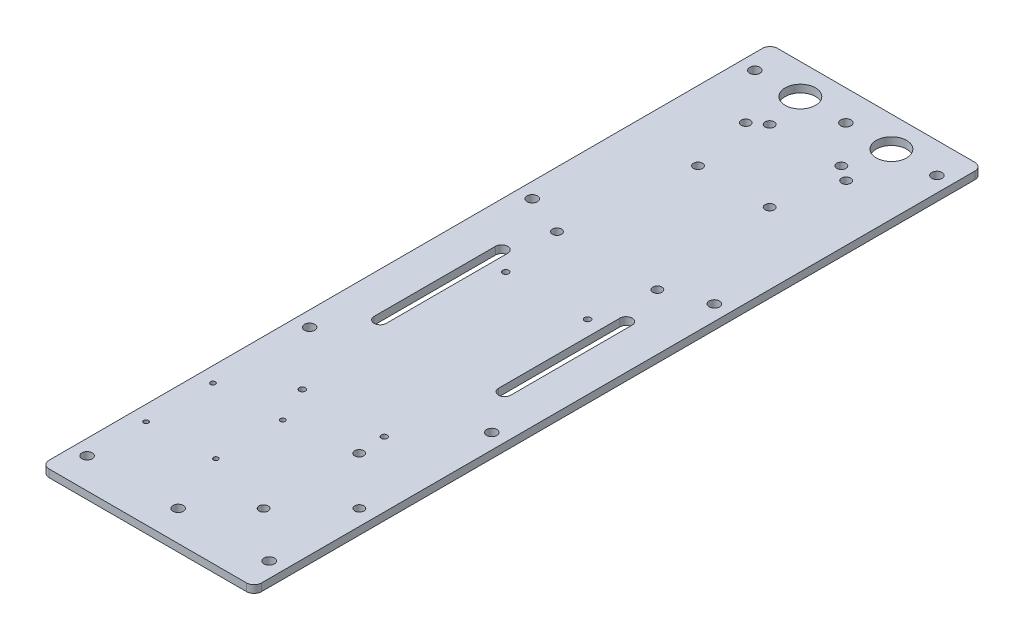
SolidWorks part; units mm, degrees
ref_plane "Front Plane" through (0, 0, 0) normal (0, 0, 1) x (1, 0, 0)
ref_plane "Top Plane" through (0, 0, 0) normal (0, 1, 0) x (1, 0, 0)
ref_plane "Right Plane" through (0, 0, 0) normal (1, 0, 0) x (0, 0, -1)
sketch "Sketch2" plane through (0, 0, 0) normal (0, 1, 0) x (1, 0, 0)
  line L0 (-44.45, 0) -> (44.45, 0) construction
  line L1 (-41.275, 152.4) -> (41.275, 152.4)
  line L2 (-44.45, 149.225) -> (-44.45, -149.225)
  line L3 (-41.275, -152.4) -> (41.275, -152.4)
  line L4 (44.45, 149.225) -> (44.45, -149.225)
  line L5 (0, 152.4) -> (0, -152.4) construction
  arc A0 (-44.45, -149.225) -> (-41.275, -152.4) centre (-41.275, -149.225) ccw
  arc A1 (41.275, -152.4) -> (44.45, -149.225) centre (41.275, -149.225) ccw
  arc A2 (41.275, 152.4) -> (44.45, 149.225) centre (41.275, 149.225) cw
  arc A3 (-41.275, 152.4) -> (-44.45, 149.225) centre (-41.275, 149.225) ccw
  point P8 (0, 0)
  point P13 (-44.45, -152.4)
  point P16 (44.45, -152.4)
  point P21 (-44.45, 152.4)
  dimension "D3" = 3.175
  dimension "D1" = 304.8
  dimension "D2" = 88.9
extrude "Plate Thickness" add sketch "Sketch2" along normal blind 3.175 contours L2 A0 L3 A1 L4 A2 L1 A3
sketch "Sketch3" plane through (0, 3.175, 0) normal (0, 1, 0) x (1, 0, 0)
  line L0 (-44.45, 149.225) -> (-44.45, -149.225) construction
  line L1 (-41.275, 152.4) -> (41.275, 152.4) construction
  line L4 (0, 152.4) -> (0, -152.4) construction
  line L5 (-41.275, -152.4) -> (41.275, -152.4) construction
  line L6 (-41.275, -152.4) -> (41.275, -152.4) construction
  circle A0 centre (-38.1, 139.7) radius 2.159
  circle A1 centre (-38.1, 46.5667) radius 2.159
  circle A2 centre (-38.1, -46.5667) radius 2.159
  circle A3 centre (-38.1, -139.7) radius 2.159
  circle A4 centre (38.1, -139.7) radius 2.159
  circle A5 centre (38.1, -46.5667) radius 2.159
  circle A6 centre (38.1, 46.5667) radius 2.159
  circle A7 centre (38.1, 139.7) radius 2.159
  circle A8 centre (0, 139.7) radius 2.159
  circle A9 centre (0, -139.7) radius 2.159
  dimension "D1" = 4.318
  dimension "D4" = 4.318
  dimension "D2" = 6.35
  dimension "D3" = 12.7
  dimension "D5" = 12.7
  dimension "D6" = 12.7
  dimension "D7" = 93.1333
  dimension "D8" = 93.1333
extrude "Mounting holes" cut sketch "Sketch3" against normal through all
sketch "Sketch4" plane through (0, 3.175, 0) normal (0, 1, 0) x (1, 0, 0)
  line L0 (-21.0058, 39.8143) -> (21.0058, 39.8143) construction
  line L1 (0, 0) -> (0, 139.7) construction
  circle A0 centre (-21.0058, 118.8083) radius 1.905
  circle A1 centre (-21.0058, 39.8143) radius 1.905
  circle A2 centre (21.0058, 39.8143) radius 1.905
  circle A3 centre (21.0058, 118.8083) radius 1.905
  point P13 (0, 39.8143)
  point P17 (0, 69.85)
  point P18 (0, 69.85)
  dimension "D1" = 3.81
  dimension "D2" = 78.994
  dimension "D3" = 42.0116
extrude "Jetson Holes (w/o mount)" cut sketch "Sketch4" against normal through all
sketch "Sketch5" plane through (0, 3.175, 0) normal (0, 1, 0) x (1, 0, 0)
  line L0 (-41.275, 152.4) -> (41.275, 152.4) construction
  line L1 (44.45, 149.225) -> (44.45, -149.225) construction
  circle A1 centre (-15.3784, 123.19) radius 1.905
  circle A3 centre (14.619, 123.19) radius 1.905
  circle A4 centre (14.619, 93.1926) radius 1.905
  circle A5 centre (-15.3784, 93.1926) radius 1.905
  dimension "D1" = 3.81
  dimension "D2" = 29.9974
  dimension "D4" = 29.21
  dimension "D5" = 29.831
  dimension "D3" = 29.9974
extrude "PDB holes" cut sketch "Sketch5" against normal through all
sketch "Sketch6" plane through (0, 3.175, 0) normal (0, 1, 0) x (1, 0, 0)
  circle A6 centre (37.9175, -101.7966) radius 1.905
  circle A7 centre (17.9175, -81.8626) radius 1.905
  circle A8 centre (17.9175, -121.8626) radius 1.905
  dimension "D5" = 3.81
  dimension "D6" = 40
  dimension "D7" = 20
  dimension "D8" = 20.066
sketch "Sketch7" plane through (0, 3.175, 0) normal (0, 1, 0) x (1, 0, 0)
  line L0 (0, 152.4) -> (0, -152.4) construction
  line L1 (-41.275, 152.4) -> (41.275, 152.4) construction
  line L2 (-41.275, -152.4) -> (41.275, -152.4) construction
  line L3 (17.145, 14.4893) -> (-17.145, 14.4893) construction
  circle A0 centre (-17.145, 14.4893) radius 1.27
  circle A1 centre (-17.145, -70.6007) radius 1.27
  circle A2 centre (17.145, -70.6007) radius 1.27
  circle A3 centre (17.145, 14.4893) radius 1.27
  point P14 (0, 14.4893)
  dimension "D1" = 2.54
  dimension "D2" = 85.09
  dimension "D3" = 34.29
extrude "PixHawk Holes" cut sketch "Sketch7" against normal through all
sketch "Sketch8" plane through (0, 3.175, 0) normal (0, 1, 0) x (1, 0, 0)
  line L0 (0, 152.4) -> (0, -115.5095) construction
  line L1 (-41.275, 152.4) -> (41.275, 152.4) construction
  line L2 (-26.035, 21.6897) -> (-26.035, -29.1103) construction
  line L3 (-23.495, 21.6897) -> (-23.495, -29.1103)
  line L4 (-28.575, 21.6897) -> (-28.575, -29.1103)
  line L5 (26.035, 21.6897) -> (26.035, -29.1103) construction
  line L6 (23.495, 21.6897) -> (23.495, -29.1103)
  line L7 (28.575, 21.6897) -> (28.575, -29.1103)
  arc A0 (-23.495, 21.6897) -> (-28.575, 21.6897) centre (-26.035, 21.6897) ccw
  arc A1 (-28.575, -29.1103) -> (-23.495, -29.1103) centre (-26.035, -29.1103) ccw
  arc A2 (23.495, 21.6897) -> (28.575, 21.6897) centre (26.035, 21.6897) cw
  arc A3 (28.575, -29.1103) -> (23.495, -29.1103) centre (26.035, -29.1103) cw
  point P7 (-26.035, -3.7103)
  point P14 (26.035, -3.7103)
  point P19 (0, 0)
  point P20 (-26.035, -8.3266)
  point P21 (0, 0)
  point P22 (0, 0)
  point P23 (0, 0)
  point P24 (-26.035, -3.7103)
  dimension "D1" = 50.8
  dimension "D2" = 5.08
  dimension "D3" = 26.035
extrude "Battery Holes" cut sketch "Sketch8" against normal through all
sketch "Sketch9" plane through (0, 3.175, 0) normal (0, 1, 0) x (1, 0, 0)
  line L0 (44.45, 149.225) -> (44.45, -149.225) construction
  line L1 (-41.275, -152.4) -> (41.275, -152.4) construction
  circle A0 centre (6.8334, -85.3) radius 2
  circle A1 centre (34.3334, -85.3) radius 2
  circle A2 centre (34.3334, -114.3) radius 2
  circle A3 centre (6.8334, -114.3) radius 2
  dimension "D1" = 4
  dimension "D3" = 10.1166
  dimension "D5" = 38.1
  dimension "D2" = 27.5
  dimension "D4" = 29
sketch "Sketch10" plane through (0, 3.175, 0) normal (0, 1, 0) x (1, 0, 0)
  line L0 (-44.45, 149.225) -> (-44.45, -149.225) construction
  circle A0 centre (-38.1255, -87.0086) radius 1
  circle A1 centre (-38.1, -115.0086) radius 1
  circle A2 centre (-10.1266, -85.7891) radius 1
  circle A3 centre (-10.1266, -113.7891) radius 1
  dimension "D1" = 2
  dimension "D2" = 28
  dimension "D3" = 28
  dimension "D4" = 28
  dimension "D5" = 6.35
extrude "Ventral Camera holes" cut sketch "Sketch10" against normal up to next
sketch "Sketch12" plane through (0, 3.175, 0) normal (0, 1, 0) x (1, 0, 0)
  line L0 (-41.275, 152.4) -> (41.275, 152.4) construction
  circle A0 centre (-19.05, 139.7) radius 6.35
  circle A1 centre (19.05, 139.7) radius 6.35
  circle A2 centre (-38.1, 139.7) radius 2.159 construction
  dimension "D1" = 19.05
  dimension "D3" = 12.7
  dimension "D2" = 38.1
  dimension "D4" = 12.7
extrude "Wifi antenna holes" cut sketch "Sketch12" against normal through all
extrude "Cut-Extrude1" cut sketch "Sketch6" against normal through all
